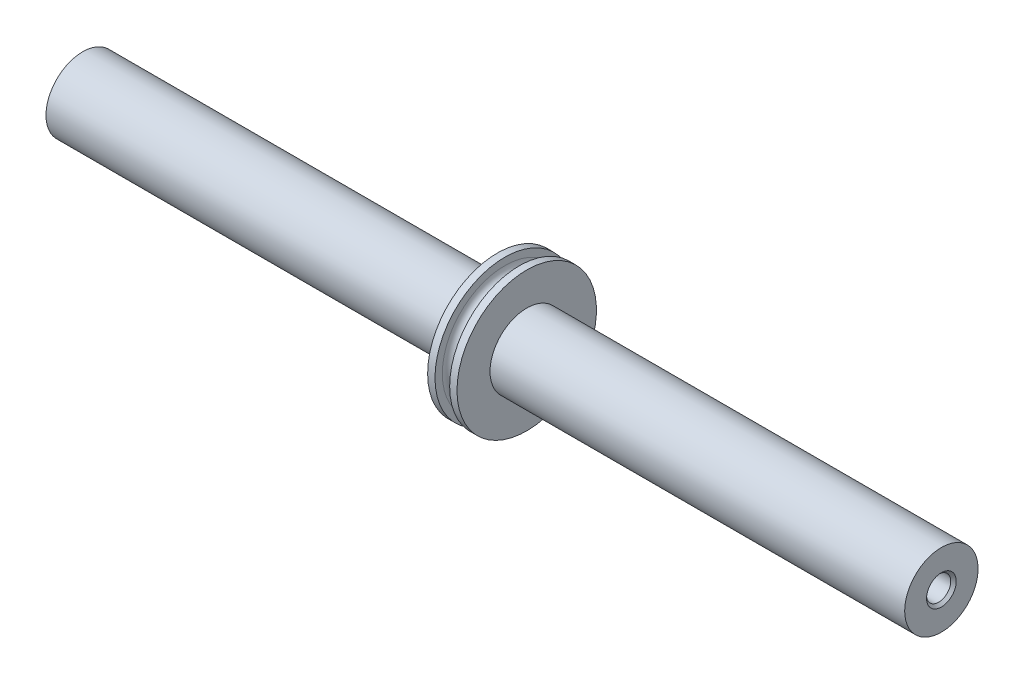
SolidWorks part; units mm, degrees
ref_plane "Front Plane" through (0, 0, 0) normal (0, 0, 1) x (1, 0, 0)
ref_plane "Top Plane" through (0, 0, 0) normal (0, 1, 0) x (1, 0, 0)
ref_plane "Right Plane" through (0, 0, 0) normal (1, 0, 0) x (0, 0, -1)
sketch "Sketch1" plane through (0, 0, 0) normal (0, 1, 0) x (1, 0, 0)
  line L0 (0, -55) -> (0, 55) construction
  line L1 (1, 0) -> (-1, 0)
  line L2 (0, 0) -> (0, 7.5)
  line L3 (1, 7.5) -> (-1, 7.5)
  line L4 (-1, 0) -> (-1, 7.5)
  line L5 (-1, 0) -> (-2, 0)
  line L6 (-1, 0) -> (-1, 9.5)
  line L7 (-1, 9.5) -> (-2, 9.5)
  line L8 (-2, 0) -> (-2, 9.5)
  line L9 (2, 0) -> (2, 9.5)
  line L10 (1, 9.5) -> (2, 9.5)
  line L11 (1, 0) -> (1, 9.5)
  line L12 (1, 0) -> (2, 0)
  line L13 (1, 0) -> (1, 7.5)
  line L14 (-2.6468, 0) -> (2.6468, 0) construction
  line L15 (2, 0) -> (58.5, 0)
  line L16 (-2, 0) -> (-58.5, 0)
  line L17 (-2, 0) -> (-2, 5)
  line L18 (-2, 5) -> (-58.5, 5)
  line L19 (-58.5, 0) -> (-58.5, 5)
  line L20 (58.5, 0) -> (58.5, 5)
  line L21 (2, 5) -> (58.5, 5)
  point P20 (0, 0)
  dimension "D1" = 7.5
  dimension "D2" = 1
  dimension "D3" = 1
  dimension "D4" = 2
  dimension "D6" = 117
  dimension "D7" = 10
revolve "Revolve1" add sketch "Sketch1" angle 360 about L14 region at (0.5, 0, -3.75) region at (1.5, 0, -4.75) region at (-0.5, 0, -3.75) region at (30.25, 0, -2.5) region at (-1.5, 0, -4.75) region at (-30.25, 0, -2.5)
fillet "Fillet1" radius 1 2 edges at (1, 0, 7.5) (-1, 0, 7.5)
hole_wizard "M4x0.7 Tapped Hole1" positions "3DSketch2" profile "Sketch3" tap size "M4x0.7" standard "ANSI Metric"
sketch3d "3DSketch2"
  circle A0 centre (-58.5, 0, 0) radius 5 construction
  point P0 (-58.5, 0, 0)
  point P6 (-63.5, 0, 0)
sketch "Sketch3" plane through (-58.5, 0, 0) normal (0, 1, 0) x (0, 0, 1)
  line L0 (0, 0) -> (0, 15.9914)
  line L1 (0, 15.9914) -> (1.65, 15)
  line L2 (1.65, 15) -> (1.65, 0.375)
  line L3 (1.65, 0.375) -> (2.025, 0)
  line L5 (2.025, 0) -> (0, 0)
  line L6 (-1.65, 0.375) -> (-2.025, 0) construction
  line L10 (0, 15.9914) -> (-1.65, 15) construction
  line L11 (0, -6.35) -> (0, 107.95) construction
  dimension "Tap Drill Dia." = 3.3
  dimension "Tap Drill Depth" = 15
  dimension "Near C'Sink Dia." = 4.05
  dimension "Near C'Sink Angle" = 90
  dimension "Drill Angle" = 118
cosmetic thread "Hole Thread1" parameters "D1"=8, "D2"=4
mirror "Mirror1" about plane through (0, 0, 0) normal (1, 0, 0) of "M4x0.7 Tapped Hole1"
cosmetic thread "Hole Thread2" parameters "D1"=8, "D2"=4
